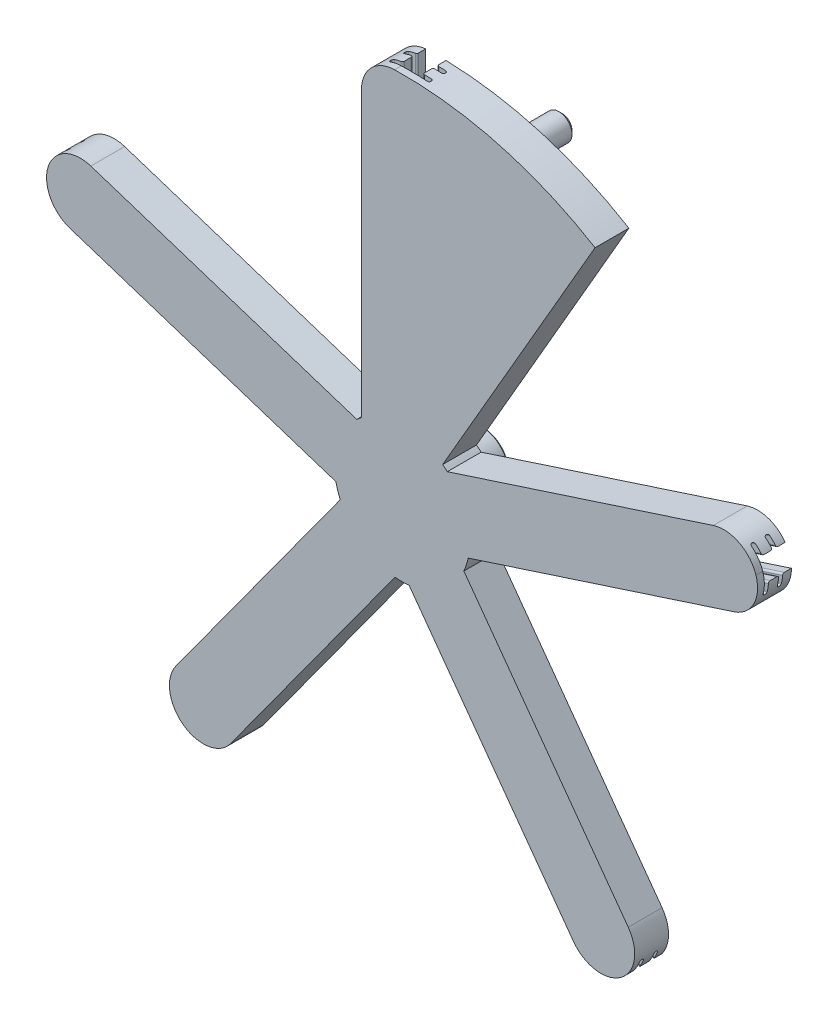
SolidWorks part; units mm, degrees
ref_plane "Front Plane" through (0, 0, 0) normal (0, 0, 1) x (1, 0, 0)
ref_plane "Top Plane" through (0, 0, 0) normal (0, 1, 0) x (1, 0, 0)
ref_plane "Right Plane" through (0, 0, 0) normal (1, 0, 0) x (0, 0, -1)
sketch "Sketch1" plane through (0, 0, 0) normal (0, 0, 1) x (1, 0, 0)
  line L0 (0, 0) -> (0, 55) construction
  line L1 (0, 0) -> (52.3081, 16.9959) construction
  line L2 (0, 0) -> (32.3282, -44.4959) construction
  line L3 (0, 0) -> (-32.3282, -44.4959) construction
  line L4 (0, 0) -> (-52.3081, 16.9959) construction
  line L5 (-50.5464, 21.6808) -> (-6.6913, 7.4314)
  line L6 (-53.6366, 12.1703) -> (-9.7815, -2.0791)
  line L7 (5, 54.7723) -> (5, 8.6603) [skipped]
  line L8 (-5, 54.7723) -> (-5, 8.6603) [skipped]
  line L9 (53.6366, 12.1703) -> (9.7815, -2.0791)
  line L10 (50.5464, 21.6808) -> (6.6913, 7.4314)
  line L11 (28.1492, -47.2506) -> (1.0453, -9.9452)
  line L12 (36.2394, -41.3728) -> (9.1355, -4.0674)
  line L13 (-36.2394, -41.3728) -> (-9.1355, -4.0674)
  line L14 (-28.1492, -47.2506) -> (-1.0453, -9.9452)
  line L15 (-6, 54.6717) -> (-6, 8)
  line L16 (28.5294, 47.0221) -> (6, 8)
  arc A0 (-36.2394, -41.3728) -> (-28.1492, -47.2506) centre (0, 0) ccw
  arc A1 (-6, 8) -> (-6.6913, 7.4314) centre (0, 0) ccw
  arc A2 (28.1492, -47.2506) -> (36.2394, -41.3728) centre (0, 0) ccw
  arc A3 (53.6366, 12.1703) -> (50.5464, 21.6808) centre (0, 0) ccw
  arc A4 (-50.5464, 21.6808) -> (-53.6366, 12.1703) centre (0, 0) ccw
  arc A5 (28.5294, 47.0221) -> (-6, 54.6717) centre (0, 0) ccw
  arc A6 (-9.7815, -2.0791) -> (-9.1355, -4.0674) centre (0, 0) ccw
  arc A7 (-1.0453, -9.9452) -> (1.0453, -9.9452) centre (0, 0) ccw
  arc A8 (9.1355, -4.0674) -> (9.7815, -2.0791) centre (0, 0) ccw
  arc A9 (6.6913, 7.4314) -> (6, 8) centre (0, 0) ccw
  point P12 (0, 0)
  point P33 (0, 0)
  dimension "D3" = 20
  dimension "D1" = 55
  dimension "D4" = 5
  dimension "D6" = 6
  dimension "D7" = 30
  dimension "D8" = 6
  dimension "D2" = 5
  dimension "D5" = 5
extrude "Boss-Extrude1" add sketch "Sketch1" along normal blind 5
fillet "Fillet1" radius 5 9 edges at (50.5464, 21.6808, 2.5) (53.6366, 12.1703, 2.5) (36.2394, -41.3728, 2.5) (28.1492, -47.2506, 2.5) (-28.1492, -47.2506, 2.5) (-36.2394, -41.3728, 2.5) (-53.6366, 12.1703, 2.5) (-50.5464, 21.6808, 2.5) (-6, 54.6717, 2.5)
ref_plane "Plane1" through (-5.0904, -7.0063, 0) normal (0.5878, 0.809, 0) x (0.809, -0.5878, 0)
sketch "Sketch2" plane through (-5.0904, -7.0063, 0) normal (0.5878, 0.809, 0) x (0.809, -0.5878, 0)
  line L0 (0, 0) -> (0, -4) construction
  line L1 (0, -5) -> (0, 0) construction
  line L2 (0, 0) -> (1.5, 0)
  line L3 (5, 0) -> (0, 0) construction
  line L4 (1.5, 0) -> (1.5, -1.05)
  line L5 (1.75, -1.3) -> (2.75, -1.3)
  line L6 (3, -1.55) -> (3, -1.65)
  line L7 (2.75, -1.9) -> (1.75, -1.9)
  line L8 (1.5, -2.15) -> (1.5, -3.15)
  line L9 (1.75, -3.4) -> (2.75, -3.4)
  line L10 (3, -3.65) -> (3, -3.75)
  line L11 (2.75, -4) -> (-2.75, -4)
  line L12 (-3, -3.65) -> (-3, -3.75)
  line L13 (-1.75, -3.4) -> (-2.75, -3.4)
  line L14 (-1.5, -2.15) -> (-1.5, -3.15)
  line L15 (-2.75, -1.9) -> (-1.75, -1.9)
  line L16 (-3, -1.55) -> (-3, -1.65)
  line L17 (-1.75, -1.3) -> (-2.75, -1.3)
  line L18 (-1.5, 0) -> (-1.5, -1.05)
  line L19 (0, 0) -> (-1.5, 0)
  arc A0 (1.5, -3.15) -> (1.75, -3.4) centre (1.75, -3.15) ccw
  arc A1 (1.75, -1.9) -> (1.5, -2.15) centre (1.75, -2.15) ccw
  arc A2 (1.5, -1.05) -> (1.75, -1.3) centre (1.75, -1.05) ccw
  arc A3 (3, -1.65) -> (2.75, -1.9) centre (2.75, -1.65) cw
  arc A4 (2.75, -1.3) -> (3, -1.55) centre (2.75, -1.55) cw
  arc A5 (3, -3.75) -> (2.75, -4) centre (2.75, -3.75) cw
  arc A6 (2.75, -3.4) -> (3, -3.65) centre (2.75, -3.65) cw
  arc A7 (-2.75, -3.4) -> (-3, -3.65) centre (-2.75, -3.65) ccw
  arc A8 (-3, -3.75) -> (-2.75, -4) centre (-2.75, -3.75) ccw
  arc A9 (-2.75, -1.3) -> (-3, -1.55) centre (-2.75, -1.55) ccw
  arc A10 (-3, -1.65) -> (-2.75, -1.9) centre (-2.75, -1.65) ccw
  arc A11 (-1.5, -1.05) -> (-1.75, -1.3) centre (-1.75, -1.05) cw
  arc A12 (-1.75, -1.9) -> (-1.5, -2.15) centre (-1.75, -2.15) cw
  arc A13 (-1.5, -3.15) -> (-1.75, -3.4) centre (-1.75, -3.15) cw
  point P17 (1.5, -3.4)
  point P20 (1.5, -1.9)
  point P25 (3, -1.9)
  point P30 (3, -4)
  point P33 (3, -3.4)
  point P56 (-3, -3.4)
  point P57 (-3, -4)
  point P58 (-3, -1.9)
  point P59 (-1.5, -1.9)
  point P60 (-1.5, -3.4)
  dimension "D6" = 0.25
  dimension "D7" = 0.25
  dimension "D8" = 0.25
  dimension "D1" = 4
  dimension "D2" = 0.6
  dimension "D3" = 1.5
  dimension "D4" = 1.5
  dimension "D5" = 3
extrude "Cut-Extrude2" cut sketch "Sketch2" against normal blind 51
pattern_circular "CirPattern1" count 5 over 360 about axis through (0, 0, 5) along (0, 0, -1) of "Cut-Extrude2" reverse direction yes
sketch "Sketch3" plane through (0, 0, 0) normal (0, 0, -1) x (-1, 0, 0)
  line L0 (0, 0) -> (0, 43.526) construction
  line L1 (0, 0) -> (-11.672, 48.3203) construction
  circle A0 centre (-11.672, 48.3203) radius 1.95
  dimension "D3" = 3.9
  dimension "D1" = 13.58
  dimension "D2" = 49.71
extrude "Boss-Extrude2" add sketch "Sketch3" along normal blind 7
chamfer "Chamfer1" distance 0.5 angle 45 1 edges at (9.722, 48.3203, -7)
sketch "Sketch4" plane through (0, 0, 0) normal (0, 0, -1) x (-1, 0, 0)
  circle A0 centre (0, 0) radius 3.975
  dimension "D1" = 7.95
extrude "Boss-Extrude3" add sketch "Sketch4" along normal blind 7
chamfer "Chamfer2" distance 0.25 angle 45 1 edges at (-3.975, 0, -7)
